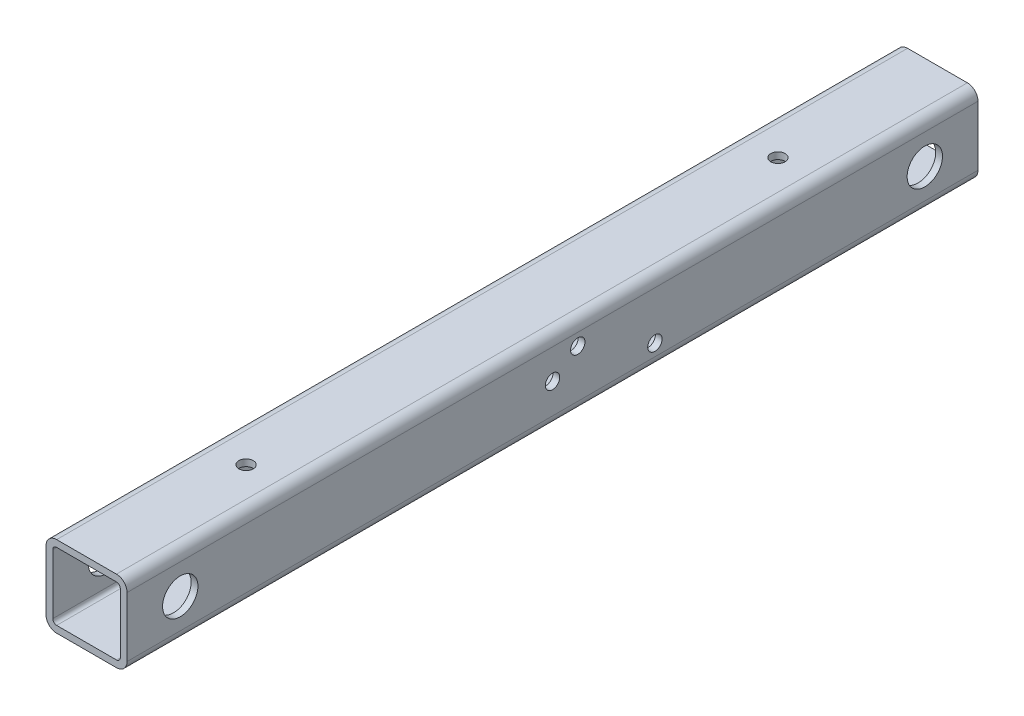
SolidWorks part; units mm, degrees
ref_plane "Front Plane" through (0, 0, 0) normal (0, 0, 1) x (1, 0, 0)
ref_plane "Top Plane" through (0, 0, 0) normal (0, 1, 0) x (1, 0, 0)
ref_plane "Right Plane" through (0, 0, 0) normal (1, 0, 0) x (0, 0, -1)
sketch "Sketch1" plane through (0, 0, 0) normal (0, 0, 1) x (1, 0, 0)
  line L6 (-14.05, 19.05) -> (14.05, 19.05)
  line L7 (19.05, 14.05) -> (19.05, -14.05)
  line L8 (-15.875, 14.05) -> (-15.875, -14.05)
  line L9 (-14.05, -15.875) -> (14.05, -15.875)
  line L10 (14.05, -19.05) -> (-14.05, -19.05)
  line L11 (-19.05, -14.05) -> (-19.05, 14.05)
  line L12 (0, 19.05) -> (0, -19.05) construction
  line L13 (-19.05, 0) -> (19.05, 0) construction
  line L14 (15.875, -14.05) -> (15.875, 14.05)
  line L15 (14.05, 15.875) -> (-14.05, 15.875)
  line L16 (0, 15.875) -> (0, -15.875) construction
  line L17 (-15.875, 0) -> (15.875, 0) construction
  arc A0 (14.05, 19.05) -> (19.05, 14.05) centre (14.05, 14.05) cw
  arc A1 (19.05, -14.05) -> (14.05, -19.05) centre (14.05, -14.05) cw
  arc A2 (-14.05, -19.05) -> (-19.05, -14.05) centre (-14.05, -14.05) cw
  arc A3 (-19.05, 14.05) -> (-14.05, 19.05) centre (-14.05, 14.05) cw
  arc A4 (-15.875, -14.05) -> (-14.05, -15.875) centre (-14.05, -14.05) ccw
  arc A5 (14.05, -15.875) -> (15.875, -14.05) centre (14.05, -14.05) ccw
  arc A6 (15.875, 14.05) -> (14.05, 15.875) centre (14.05, 14.05) ccw
  arc A7 (-14.05, 15.875) -> (-15.875, 14.05) centre (-14.05, 14.05) ccw
  point P40 (0, 0)
  dimension "D3" = 5
  dimension "D4" = 3.175
extrude "Boss-Extrude1" add sketch "Sketch1" along normal blind 400
sketch "Sketch2" plane through (0, 0, 0) normal (1, 0, 0) x (0, 0, -1)
  line L0 (-375, 0) -> (-25, 0) construction
  line L1 (20.955, 0) -> (-20.955, 0) construction
  line L2 (0, 20.955) -> (0, -20.955) construction
  circle A0 centre (-375, 0) radius 8.3125
  circle A1 centre (-25, 0) radius 8.3125
  dimension "D4" = 16.625
  dimension "D2" = 350
  dimension "D1" = 25
extrude "Cut-Extrude1" cut sketch "Sketch2" against normal through all both and the other way through all
sketch "Sketch3" plane through (0, 0, 0) normal (0, 1, 0) x (1, 0, 0)
  line L0 (0, -325) -> (0, -75) construction
  line L1 (0, -20.955) -> (0, 20.955) construction
  circle A0 centre (0, -325) radius 3.38
  circle A1 centre (0, -75) radius 3.38
  dimension "D4" = 6.76
  dimension "D2" = 250
  dimension "D3" = 75
extrude "Cut-Extrude2" cut sketch "Sketch3" along normal through all both and the other way through all
sketch "Centrepoint" plane through (0, 0, 0) normal (1, 0, 0) x (0, 0, -1)
  point P0 (-200, 0)
  dimension "D1" = 200
sketch "Sketch4" plane through (0, 0, 0) normal (1, 0, 0) x (0, 0, -1)
  line L0 (0, 20.955) -> (0, -20.955) construction
  line L1 (20.955, 0) -> (-20.955, 0) construction
  circle A0 centre (-200, 0) radius 3.38
  dimension "D1" = 6.76
  dimension "D2" = 200
extrude "Cut-Extrude3" cut sketch "Sketch4" against normal through all both and the other way through all
sketch "Sketch5" plane through (0, 0, 0) normal (1, 0, 0) x (0, 0, -1)
  line L0 (-188.1262, 8.4524) -> (-151.8738, -8.4524) construction
  line L1 (20.955, 0) -> (-20.955, 0) construction
  line L2 (0, 20.955) -> (0, -20.955) construction
  circle A0 centre (-188.1262, 8.4524) radius 3.38
  circle A1 centre (-151.8738, -8.4524) radius 3.38
  point P4 (-170, 0)
  dimension "D1" = 6.76
  dimension "D2" = 25
  dimension "D3" = 40
  dimension "D4" = 170
extrude "Cut-Extrude4" cut sketch "Sketch5" against normal through all both and the other way through all
equation "\"shovelHoleDiameter\"= 5in / 8 + 0.75"
equation "\"D4@Sketch2\"=\"shovelHoleDiameter\""
equation "\"mountHoleDiameter\"= 6.76mm"
equation "\"D4@Sketch3\"=\"mountHoleDiameter\""
equation "\"limitSwitchHoleDiameter\"= 6.76mm"
equation "\"D1@Sketch4\"=\"limitSwitchHoleDiameter\""
equation "\"bracketWidth\"= 400mm"
equation "\"mountingHoleDistance\"= 250mm"
equation "\"shovelHoleDistance\"= 350mm"
equation "\"D2@Sketch2\"=\"shovelHoleDistance\""
equation "\"D2@Sketch3\"=\"mountingHoleDistance\""
equation "\"D3@Sketch3\"=(\"bracketWidth\"-\"mountingHoleDistance\")/2"
equation "\"D2@Sketch4\"=\"bracketWidth\"/2"
equation "\"D1@Sketch5\"=\"mountHoleDiameter\""
equation "\"D4@Sketch5\"=\"bracketWidth\"/2 -30"
